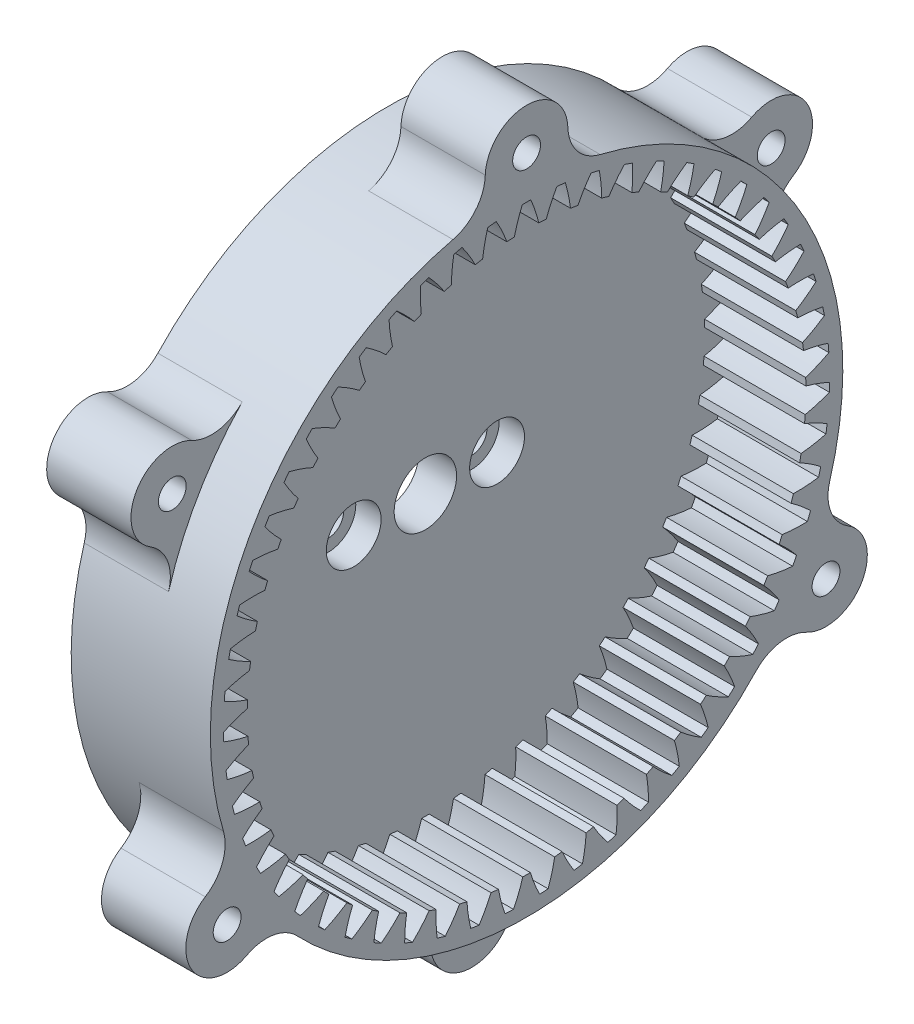
SolidWorks part; units mm, degrees
ref_plane "Plane1" through (0, 0, 0) normal (0, 0, 1) x (1, 0, 0)
ref_plane "Plane2" through (0, 0, 0) normal (0, 1, 0) x (1, 0, 0)
ref_plane "Plane3" through (0, 0, 0) normal (1, 0, 0) x (0, 0, -1)
sketch "HoldingSke" plane through (0, 0, 0) normal (0, 1, 0) x (1, 0, 0)
  line L0 (0, 0) -> (0.4589, -0.6553)
  line L1 (-15, 0) -> (100, 0) construction
  line L2 (0, 0) -> (-2.1039, 2.3779)
  line L3 (0, 0) -> (-11.863, 4.5341)
  line L4 (0, 0) -> (4.9534, 7.0742)
  line L5 (0, 0) -> (-23.7986, -8.8762)
  line L6 (0, 0) -> (-10.5278, -7.1032)
  line L7 (-2.1039, 2.3779) -> (3.3635, 27.1825)
  line L8 (-76.2, 3.6279) -> (-54.61, 3.6279)
  line L9 (-67.7845, 28.3722) -> (-49.3413, 33.142)
  line L10 (-76.2, 71.12) -> (104.1128, 71.12)
  line L11 (0, 0) -> (-12, 0)
  line L12 (-76.2, 101.6) -> (-76.155, 101.6)
  line L13 (24.9733, 27.94) -> (52.9518, 28.4284)
  line L14 (24.9733, 27.94) -> (24.9743, 27.94)
  line L15 (24.9733, 27.94) -> (100.4006, 29.5858)
  circle A0 centre (0, 0) radius 37.5
  circle A1 centre (0, 0) radius 12.7
  circle A2 centre (0, 0) radius 12.7
  dimension "MHD" = 25.4
  dimension "Hub_dia" = 25.4
  dimension "Diameter" = 75
  dimension "Num_teeth" = 55
  dimension "Pitch" = 0.8
  dimension "Overall_len" = 25.4
  dimension "Show_teeth" = 55
  dimension "Thickness" = 12.7
  dimension "OAL" = 25.4001
  dimension "T_dim" = 21.59
  dimension "Ap" = 14.5
  dimension "H" = 19.05
  dimension "Pitch_radius" = 180.3128
  dimension "Width" = 12
  dimension "Backlash" = 0.045
  dimension "Addendum_fac" = 1
  dimension "Dedendum_fac" = 1.25
  dimension "Clearance_fac" = 0.25
  dimension "Dedendum_add" = 0.001
  dimension "Module" = 1.25
sketch "BasProSke" plane through (0, 0, 0) normal (0, 1, 0) x (1, 0, 0)
  line L0 (-10, 0) -> (60, 0) construction
  line L1 (0, 33.125) -> (0, 37.5)
  line L2 (0, 33.125) -> (12, 33.125)
  line L3 (12, 33.125) -> (12, 37.5)
  line L4 (12, 37.5) -> (0, 37.5)
  dimension "Diameter" = 75
  dimension "Thickness" = 12
  dimension "Inside_diameter" = 66.25
revolve "Base-Revolve" add sketch "BasProSke" angle 360 about L0
sketch "TooCutSke" plane through (0, 0, 0) normal (1, 0, 0) x (0, 0, -1)
  line L3 (1.0941, 34.3576) -> (1.0941, 53.6633) construction
  line L4 (0, 0) -> (0, 59.563) construction
  line L5 (0, 0) -> (-3.9007, 68.2161) construction
  line L6 (-15.2783, 29.1274) -> (36.0712, 32.0636) construction
  circle A0 centre (0, 0) radius 34.375 construction
  circle A1 centre (0, 0) radius 35.9385 construction
  circle A2 centre (0, 0) radius 29.9521 construction
  circle A3 centre (0, 0) radius 33.0996 construction
  arc A4 (1.4514, 33.0678) -> (0.5036, 35.935) centre (-15.2783, 29.1274) ccw
  arc A5 (1.4514, 33.0678) -> (-1.4514, 33.0678) centre (0, 0) ccw
  arc A6 (0.5036, 35.935) -> (-0.5036, 35.935) centre (0, 0) ccw
  arc A7 (-0.5036, 35.935) -> (-1.4514, 33.0678) centre (15.2783, 29.1274) ccw
  dimension "Pitch_dia" = 68.75
  dimension "Base_dia" = 59.9041
  dimension "Root_dia" = 71.877
  dimension "Overcut_dia" = 66.1992
  dimension "Flank_rad" = 17.1875
  dimension "Half_ang" = 3.273
  dimension "Half_CT" = 1.0941
extrude "ToothCut" cut sketch "TooCutSke" along normal through all
fillet "Breaks" [suppressed] radius 0.125
fillet "RootFillets" [suppressed] radius 0.3135
pattern_circular "TeethCuts" count 55 every 6.545 about axis through (-10, 0, 0) along (1, 0, 0) of "RootFillets", "Breaks", "ToothCut"
sketch "Sketch2" plane through (0, 0, 0) normal (-1, 0, 0) x (0, 0, 1)
  circle A0 centre (0, 0) radius 37.5
extrude "Boss-Extrude2" add sketch "Sketch2" along normal blind 4.5
sketch "Sketch3" plane through (0, 0, 0) normal (1, 0, 0) x (0, 0, -1)
  circle A0 centre (0, 0) radius 3.7
  circle A1 centre (8.5, 0) radius 1.8
  circle A2 centre (-8.5, 0) radius 1.8
  dimension "D1" = 7.4
  dimension "D2" = 3.6
  dimension "D3" = 8.5
  dimension "D4" = 8.5
extrude "Cut-Extrude1" cut sketch "Sketch3" against normal blind 10 contours A1 | A0 | A2
sketch "Sketch4" plane through (0, 0, 0) normal (1, 0, 0) x (0, 0, -1)
  circle A0 centre (8.5, 0) radius 3.25
  circle A1 centre (-8.5, 0) radius 3.25
  dimension "D1" = 6.5
extrude "Cut-Extrude2" cut sketch "Sketch4" against normal blind 3
sketch "Sketch5" plane through (-4.5, 0, 0) normal (-1, 0, 0) x (0, 0, 1)
  line L0 (0, 0) -> (0, -41) construction
  line L1 (0, 0) -> (0, -45.9) construction
  circle A0 centre (0, -41) radius 1.65
  circle A1 centre (-35.507, 20.5) radius 1.65
  circle A2 centre (35.507, 20.5) radius 1.65
  arc A3 (3.2765, -37.3566) -> (-3.2765, -37.3566) centre (0, -41) cw
  circle A4 centre (0, 0) radius 37.5 construction
  arc A5 (3.2765, -37.3566) -> (-3.2765, -37.3566) centre (0, 0) cw
  arc A6 (-33.99, 15.8408) -> (-30.7135, 21.5158) centre (-35.507, 20.5) cw
  arc A7 (-33.99, 15.8408) -> (-30.7135, 21.5158) centre (0, 0) cw
  arc A8 (30.7135, 21.5158) -> (33.99, 15.8408) centre (35.507, 20.5) cw
  arc A9 (30.7135, 21.5158) -> (33.99, 15.8408) centre (0, 0) cw
  point P11 (0, 0)
  point P25 (0, 0)
  dimension "D1" = 3.3
  dimension "D5" = 3
  dimension "D2" = 41
  dimension "D4" = 45.9
  dimension "D3" = 3
extrude "Boss-Extrude3" add sketch "Sketch5" against normal blind 10
fillet "Fillet1" radius 5 6 edges at (0.5, 15.8408, -33.99) (0.5, 21.5158, -30.7135) (0.5, 21.5158, 30.7135) (0.5, 15.8408, 33.99) (0.5, -37.3566, 3.2765) (0.5, -37.3566, -3.2765)
sketch "Sketch6" plane through (12, 0, 0) normal (1, 0, 0) x (0, 0, -1)
  line L0 (0, 0) -> (0, -41) construction
  line L1 (0, 0) -> (35.507, -20.5) construction
  line L2 (0, 0) -> (39.7506, -22.95) construction
  circle A0 centre (35.507, -20.5) radius 1.65
  circle A1 centre (-35.507, -20.5) radius 1.65
  circle A2 centre (0, 41) radius 1.65
  arc A3 (33.99, -15.8408) -> (30.7135, -21.5158) centre (35.507, -20.5) cw
  circle A4 centre (0, 0) radius 37.5 construction
  arc A5 (33.99, -15.8408) -> (30.7135, -21.5158) centre (0, 0) cw
  arc A6 (-30.7135, -21.5158) -> (-33.99, -15.8408) centre (-35.507, -20.5) cw
  arc A7 (-30.7135, -21.5158) -> (-33.99, -15.8408) centre (0, 0) cw
  arc A8 (-3.2765, 37.3566) -> (3.2765, 37.3566) centre (0, 41) cw
  arc A9 (-3.2765, 37.3566) -> (3.2765, 37.3566) centre (0, 0) cw
  point P14 (0, 0)
  point P28 (0, 0)
  dimension "D4" = 3.3
  dimension "D6" = 3
  dimension "D1" = 41
  dimension "D2" = 60
  dimension "D3" = 60
  dimension "D5" = 3
extrude "Boss-Extrude4" add sketch "Sketch6" against normal blind 10
fillet "Fillet2" radius 5 6 edges at (7, 37.3566, -3.2765) (7, 37.3566, 3.2765) (7, -15.8408, 33.99) (7, -21.5158, 30.7135) (7, -21.5158, -30.7135) (7, -15.8408, -33.99)
equation "' \"Module@HoldingSke\" = 6.35"
equation "' \"Num_teeth@HoldingSke\" = 24"
equation "' \"Ap@HoldingSke\" =  14.5"
equation "' \"Ap@HoldingSke\" = 14.5"
equation "' \"Width@HoldingSke\" = 12"
equation "' \"Diameter@HoldingSke\" = 8 * 25.4"
equation "' \"Show_teeth@HoldingSke\" = 100"
equation "' \"Backlash@HoldingSke\" = 0.009 * 25.4"
equation "' \"Addendum_fac@HoldingSke\" = 1.0"
equation "' \"Dedendum_fac@HoldingSke\" = 1.25"
equation "' \"Dedendum_add@HoldingSke\" = 0.00005 * 25.4"
equation "' \"Clearance_fac@HoldingSke\" = 0.25"
equation "\"Pitch@HoldingSke\" = 1 / \"Module@HoldingSke\" "
equation "\"Overcut_dia@TooCutSke\" = (\"Num_teeth@HoldingSke\" - 2 * \"Addendum_fac@HoldingSke\") / \"Pitch@HoldingSke\" - 0.002 * 25.4"
equation "\"Pitch_dia@TooCutSke\" = \"Num_teeth@HoldingSke\" / \"Pitch@HoldingSke\""
equation "\"Base_dia@TooCutSke\" = \"Num_teeth@HoldingSke\" / \"Pitch@HoldingSke\" * cos((\"Ap@HoldingSke\"  * 3.14159265 / 180)) * 0.90"
equation "\"Root_dia@TooCutSke\" = \"Num_teeth@HoldingSke\"  / \"Pitch@HoldingSke\" + 2 *  \"Dedendum_fac@HoldingSke\"/ \"Pitch@HoldingSke\" + \"Dedendum_add@HoldingSke\" * 2"
equation "\"Half_ang@TooCutSke\" = 180 / \"Num_teeth@HoldingSke\""
equation "\"Half_CT@TooCutSke\" = \"Num_teeth@HoldingSke\" / \"Pitch@HoldingSke\" * sin((3.14159265 / 2 / \"Num_teeth@HoldingSke\")) / 2 + 10 * \"Backlash@HoldingSke\" / 4"
equation "\"Flank_rad@TooCutSke\" = \"Num_teeth@HoldingSke\" / \"Pitch@HoldingSke\" / 4"
equation "\"Radius@RootFillets\"= \"Clearance_fac@HoldingSke\" / \"Pitch@HoldingSke\" + \"Dedendum_add@HoldingSke\""
equation "\"Break_rad@Breaks\" = 0.02 / \"Pitch@HoldingSke\" * 5"
equation "\"Num_teeth@TeethCuts\" = int( \"Show_teeth@HoldingSke\" ) + 1"
equation "\"Num_teeth@TeethCuts\" = ((sgn( \"Num_teeth@TeethCuts\" - \"Num_teeth@HoldingSke\" )-1)*( \"Num_teeth@TeethCuts\" - \"Num_teeth@HoldingSke\" ))/-2+ \"Num_teeth@HoldingSke\""
equation "\"Num_teeth@TeethCuts\" = ((sgn( \"Num_teeth@TeethCuts\" - 2.0)+1)*( \"Num_teeth@TeethCuts\" - 2.0))/2 +2.0"
equation "\"Angle@TeethCuts\" = 360.0 / \"Num_teeth@HoldingSke\""
equation "\"Diameter@BasProSke\" = \"Num_teeth@HoldingSke\"  / \"Pitch@HoldingSke\" + 2 *  \"Dedendum_fac@HoldingSke\"/ \"Pitch@HoldingSke\" + \"Dedendum_add@HoldingSke\" * 2 + 0.002 * 25.4"
equation "\"Diameter@BasProSke\" = ((sgn( \"Diameter@BasProSke\"  - \"Diameter@HoldingSke\" )+1)*( \"Diameter@BasProSke\"  - \"Diameter@HoldingSke\" ))/2 + \"Diameter@HoldingSke\""
equation "\"Inside_diameter@BasProSke\" =  (\"Num_teeth@HoldingSke\" - 2 * \"Addendum_fac@HoldingSke\") / \"Pitch@HoldingSke\" "
equation "\"Thickness@BasProSke\"  = \"Width@HoldingSke\""
